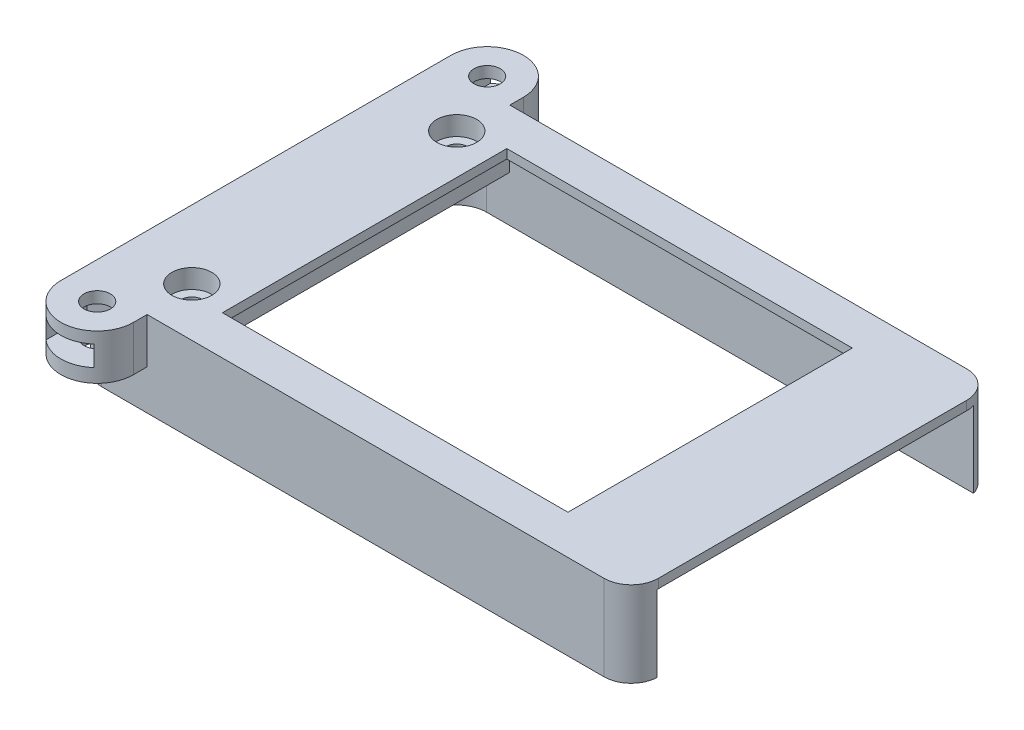
SolidWorks part; units mm, degrees
ref_plane "Front Plane" through (0, 0, 0) normal (0, 0, 1) x (1, 0, 0)
ref_plane "Top Plane" through (0, 0, 0) normal (0, 1, 0) x (1, 0, 0)
ref_plane "Right Plane" through (0, 0, 0) normal (1, 0, 0) x (0, 0, -1)
sketch "Sketch1" plane through (0, 0, 0) normal (0, 0, 1) x (1, 0, 0)
  line L0 (-23.495, -2.8321) -> (-20.447, -2.8321) construction
  line L1 (-20.447, 0) -> (-20.447, -2.8321) construction
  line L2 (-23.495, -2.8321) -> (-26.035, -2.8321) construction
  line L3 (-26.035, -2.8321) -> (-26.035, -4.4196) construction
  line L4 (-23.495, -2.8321) -> (-20.447, -2.8321) construction
  line L5 (-20.447, 0) -> (-20.447, -2.8321) construction
  line L6 (-23.495, -2.8321) -> (-26.035, -2.8321) construction
  line L7 (-26.035, -2.8321) -> (-26.035, -4.4196) construction
  line L8 (-9.4742, -6.2992) -> (-26.035, -6.2992) construction
  line L9 (-26.035, -6.2992) -> (-26.035, -4.4196) construction
  line L10 (-9.4742, -6.2992) -> (-26.035, -6.2992) construction
  line L11 (-26.035, -6.2992) -> (-26.035, -4.4196) construction
  line L12 (-20.947, 1.5) -> (-20.947, -2.8321)
  line L13 (-20.947, -2.8321) -> (-26.035, -2.8321)
  line L14 (-26.035, -2.8321) -> (-26.035, -7.9085)
  line L15 (-28.6272, -8.4085) -> (-21.9464, -8.4085) construction
  line L16 (-28.6272, -8.4085) -> (-21.9464, -8.4085) construction
  line L17 (-26.035, -7.9085) -> (-31.035, -7.9085)
  line L18 (-31.035, -7.9085) -> (-31.035, 1.5)
  line L19 (-31.035, 1.5) -> (-20.947, 1.5)
  line L20 (-20.447, 0) -> (26.0604, 0) construction
  line L21 (-20.447, 0) -> (26.0604, 0) construction
  dimension "D1" = 1
  dimension "D2" = 0.5
  dimension "D3" = 1.5
  dimension "D4" = 5
extrude "Boss-Extrude1" add sketch "Sketch1" along normal mid plane 40
sketch "Sketch2" plane through (0, 1.5, 0) normal (0, 1, 0) x (1, 0, 0)
  line L0 (-24.6493, -17.145) -> (-20.947, -17.145)
  line L1 (-20.947, -20) -> (-20.947, 20) construction
  line L2 (-20.947, -17.145) -> (-20.947, -20)
  line L3 (-20.947, -20) -> (-26.035, -20)
  line L4 (-20.947, -20) -> (-31.035, -20) construction
  line L5 (-26.035, -20) -> (-26.035, -17.145)
  line L6 (-26.035, -20) -> (-26.035, 20) construction
  line L7 (-26.035, -17.145) -> (-26.035, -15.7593)
  line L8 (-23.495, 17.895) -> (-23.495, 20)
  line L9 (-20.947, 20) -> (-31.035, 20) construction
  line L10 (-23.495, 20) -> (-26.035, 20)
  line L11 (-26.035, 20) -> (-26.035, 16.6961)
  arc A0 (-26.035, -14.605) -> (-23.495, -17.145) centre (-23.495, -14.605) ccw construction
  arc A1 (-26.035, -14.605) -> (-23.495, -17.145) centre (-23.495, -14.605) ccw construction
  arc A2 (-23.495, 17.145) -> (-26.035, 14.605) centre (-23.495, 14.605) ccw construction
  arc A3 (-23.495, 17.145) -> (-26.035, 14.605) centre (-23.495, 14.605) ccw construction
  arc A4 (-26.035, -15.7593) -> (-24.6493, -17.145) centre (-23.495, -14.605) ccw
  arc A5 (-26.285, -14.605) -> (-23.495, -17.395) centre (-23.495, -14.605) ccw construction
  arc A6 (-23.495, 17.895) -> (-26.035, 16.6961) centre (-23.495, 14.605) ccw
  arc A7 (-23.495, 17.895) -> (-26.785, 14.605) centre (-23.495, 14.605) ccw construction
  dimension "D1" = 0.25
  dimension "D2" = 0.75
extrude "Boss-Extrude2" add sketch "Sketch2" against normal up to surface (9.4085 mm away) up to face at (-28.535, -7.9085, 0)
fillet "Fillet1" radius 3 2 edges at (-31.035, -3.2043, -20) (-31.035, -3.2043, 20)
sketch "Sketch5" plane through (0, 1.5, 0) normal (0, 1, 0) x (1, 0, 0)
  line L0 (-20.947, 20) -> (27.345, 20)
  line L1 (-20.947, -20) -> (27.345, -20)
  line L2 (30.345, -17) -> (30.345, 17)
  line L3 (-20.947, -20) -> (-20.947, 20) construction
  line L4 (-20.947, -20) -> (-20.947, 20)
  line L5 (29.845, -14.605) -> (29.845, 14.605) construction
  line L8 (19.05, 15.6781) -> (19.05, -15.6781) construction
  line L9 (19.05, -15.6781) -> (-19.05, -15.6781) construction
  line L10 (19.05, 15.6781) -> (-19.05, 15.6781) construction
  line L11 (-19.05, 15.6781) -> (-19.05, -15.6781) construction
  line L12 (19.05, 15.6781) -> (19.05, -15.6781)
  line L13 (19.05, -15.6781) -> (-19.05, -15.6781)
  line L14 (19.05, 15.6781) -> (-19.05, 15.6781)
  line L15 (-19.05, 15.6781) -> (-19.05, -15.6781)
  arc A0 (27.345, -20) -> (30.345, -17) centre (27.345, -17) ccw
  arc A1 (30.345, 17) -> (27.345, 20) centre (27.345, 17) ccw
  arc A2 (-31.035, -17) -> (-28.035, -20) centre (-28.035, -17) ccw construction
  dimension "D1" = 0.5
extrude "Boss-Extrude5" add sketch "Sketch5" against normal offset from surface (1 mm away) 0.5
sketch "Sketch6" plane through (0, 0.5, 0) normal (0, -1, 0) x (1, 0, 0)
  line L0 (-23.495, 17.145) -> (27.305, 17.145) construction
  line L1 (-20.947, 17.145) -> (26.8104, 17.145)
  line L2 (26.0604, -17.145) -> (-20.447, -17.145) construction
  line L3 (-20.947, 20) -> (-20.947, -20) construction
  line L4 (-20.947, 20) -> (-20.947, 17.145)
  line L5 (27.345, 20) -> (-20.947, 20) construction
  line L6 (27.345, 20) -> (-20.947, 20)
  line L7 (-20.947, -20) -> (27.345, -20) construction
  line L8 (30.345, -17) -> (30.345, 17) construction
  line L9 (-20.947, -20) -> (27.345, -20)
  line L10 (30.345, -17) -> (30.345, 17)
  line L11 (26.0604, 17.145) -> (26.0604, 14.4018) construction
  line L12 (26.0604, 17.145) -> (26.0604, 14.4018) construction
  line L13 (26.8104, 17.145) -> (26.8104, -17.895)
  line L14 (26.0604, -17.145) -> (-20.447, -17.145) construction
  line L15 (-20.947, -20) -> (-20.947, -17.895)
  line L16 (-20.947, -17.895) -> (26.8104, -17.895)
  arc A4 (30.345, 17) -> (27.345, 20) centre (27.345, 17) ccw construction
  arc A5 (30.345, 17) -> (27.345, 20) centre (27.345, 17) ccw
  arc A6 (27.345, -20) -> (30.345, -17) centre (27.345, -17) ccw construction
  arc A7 (27.345, -20) -> (30.345, -17) centre (27.345, -17) ccw
  dimension "D2" = 1.5
extrude "Boss-Extrude6" add sketch "Sketch6" along normal up to surface (3.3321 mm away)
sketch "Sketch7" plane through (0, -2.8321, 0) normal (0, -1, 0) x (1, 0, 0)
  line L1 (-20.947, 20) -> (27.345, 20)
  line L2 (-20.947, 20) -> (-20.947, 17.145)
  line L3 (-20.947, 17.145) -> (30.3415, 17.145)
  line L6 (-23.495, -20) -> (27.345, -20)
  line L7 (-23.495, -20) -> (-23.495, -17.895)
  line L8 (-23.495, -17.895) -> (30.2084, -17.895)
  arc A0 (30.345, 17) -> (27.345, 20) centre (27.345, 17) ccw construction
  arc A1 (27.345, -20) -> (30.345, -17) centre (27.345, -17) ccw construction
  arc A2 (30.3415, 17.145) -> (27.345, 20) centre (27.345, 17) ccw
  arc A3 (27.345, -20) -> (30.2084, -17.895) centre (27.345, -17) ccw
extrude "Boss-Extrude7" add sketch "Sketch7" along normal up to surface (5.0764 mm away) up to face at (-25.9315, -7.9085, 1.3908)
sketch "Sketch9" plane through (0, 1.5, 0) normal (0, 1, 0) x (1, 0, 0)
  line L0 (-31.035, 17) -> (-31.035, 21.5)
  line L1 (-23.035, 21.5) -> (-23.035, 20)
  line L2 (27.345, 20) -> (-28.035, 20) construction
  line L3 (-23.035, 20) -> (-28.035, 20)
  line L4 (0, 0) -> (-7.0217, 0) construction
  line L5 (-23.035, -20) -> (-28.035, -20)
  line L6 (-23.035, -21.5) -> (-23.035, -20)
  line L7 (-31.035, -17) -> (-31.035, -21.5)
  arc A0 (-31.035, 21.5) -> (-23.035, 21.5) centre (-27.035, 21.5) cw
  arc A1 (-28.035, 20) -> (-31.035, 17) centre (-28.035, 17) ccw
  arc A2 (-28.035, -20) -> (-31.035, -17) centre (-28.035, -17) cw
  arc A3 (-31.035, -21.5) -> (-23.035, -21.5) centre (-27.035, -21.5) ccw
  dimension "D1" = 8
  dimension "D2" = 1.5
extrude "Boss-Extrude8" add sketch "Sketch9" against normal blind 5
hole_wizard "M2.5 Clearance Hole1" positions "Sketch10" profile "Sketch11" hole size "M2.5" standard "ANSI Metric" end condition through all
sketch "Sketch10" plane through (0, 1.5, 0) normal (0, 1, 0) x (1, 0, 0)
  point P0 (-27.035, -21.5)
  point P3 (-27.035, 21.5)
sketch "Sketch11" plane through (-27.035, 1.5, 21.5) normal (1, 0, 0) x (0, 0, 1)
  line L0 (0, 0) -> (0, 9.4085)
  line L1 (0, 9.4085) -> (1.45, 9.4085)
  line L2 (1.45, 9.4085) -> (1.45, 0)
  line L5 (1.45, 0) -> (0, 0)
  line L11 (0, -6.35) -> (0, 107.95) construction
  dimension "Thru Hole Dia." = 2.9
  dimension "Thru Hole Depth" = 9.4085
ref_plane "Plane1" through (0, -2, 0) normal (0, 1, 0) x (1, 0, 0)
sketch "Sketch12" plane through (0, -2, 0) normal (0, 1, 0) x (1, 0, 0)
  line L0 (-29.685, -23.03) -> (-29.685, -29.56)
  line L1 (-24.385, -23.03) -> (-24.385, -19.97)
  line L2 (-24.385, -19.97) -> (-27.035, -18.44)
  line L3 (-27.035, -18.44) -> (-29.685, -19.97)
  line L4 (-29.685, -19.97) -> (-29.685, -23.03)
  line L5 (-29.685, -23.03) -> (-27.035, -24.56) construction
  line L6 (-27.035, -24.56) -> (-24.385, -23.03) construction
  line L13 (-29.685, -29.56) -> (-24.385, -29.56)
  line L14 (-24.385, -29.56) -> (-24.385, -23.03)
  line L15 (0, 0) -> (-12.2155, 0) construction
  line L16 (-29.685, 23.03) -> (-29.685, 29.56)
  line L17 (-29.685, 29.56) -> (-24.385, 29.56)
  line L18 (-24.385, 29.56) -> (-24.385, 23.03)
  line L19 (-24.385, 23.03) -> (-24.385, 19.97)
  line L20 (-24.385, 19.97) -> (-27.035, 18.44)
  line L21 (-27.035, 18.44) -> (-29.685, 19.97)
  line L22 (-29.685, 19.97) -> (-29.685, 23.03)
  circle A0 centre (-27.035, -21.5) radius 2.65 construction
  circle A2 centre (-27.035, -21.5) radius 2.5 construction
  dimension "D1" = 5
  dimension "D2" = 0.15
  dimension "D3" = 5
extrude "Cut-Extrude1" cut sketch "Sketch12" along normal blind 2.25
sketch "Sketch13" plane through (0, 1.5, 0) normal (0, 1, 0) x (1, 0, 0)
  circle A0 centre (-23.495, 14.605) radius 1.016 construction
  circle A1 centre (-23.495, -14.605) radius 1.016 construction
  circle A2 centre (27.305, -14.605) radius 1.016 construction
  circle A3 centre (27.305, 14.605) radius 1.016 construction
  circle A4 centre (-23.495, 14.605) radius 1.016
  circle A5 centre (-23.495, -14.605) radius 1.016
  circle A6 centre (27.305, -14.605) radius 1.016
  circle A7 centre (27.305, 14.605) radius 1.016
hole_wizard "CBORE for M2 SHCS1" positions "Sketch14" profile "Sketch15" counterbore size "M2" standard "ANSI Metric" end condition through all
sketch "Sketch14" plane through (0, 1.5, 0) normal (0, 1, 0) x (1, 0, 0)
  point P0 (-23.495, -14.605)
  point P3 (-23.495, 14.605)
sketch "Sketch15" plane through (-23.495, 1.5, 14.605) normal (1, 0, 0) x (0, 0, 1)
  line L0 (0, 0) -> (0, 9.4085)
  line L1 (0, 9.4085) -> (1.2, 9.4085)
  line L3 (1.2, 9.4085) -> (1.2, 2.1)
  line L4 (1.2, 2.1) -> (2.2, 2.1)
  line L5 (2.2, 2.1) -> (2.2, 0)
  line L7 (2.2, 0) -> (0, 0)
  line L11 (0, -6.35) -> (0, 107.95) construction
  dimension "Thru Hole Dia." = 2.4
  dimension "Thru Hole Depth" = 9.4085
  dimension "C'Bore Dia." = 4.4
  dimension "C'Bore Depth" = 2.1
sketch "Sketch16" plane through (26.8104, 0, 0) normal (-1, 0, 0) x (0, 0, 1)
  line L4 (-17.895, 0.5) -> (-17.895, -2.8321)
  line L5 (-17.895, -2.8321) -> (17.145, -2.8321)
  line L6 (17.145, -2.8321) -> (17.145, 0.5)
  line L7 (17.145, 0.5) -> (-17.895, 0.5)
  line L8 (-17.895, 0.5) -> (-17.895, -2.8321)
  line L9 (-17.895, -2.8321) -> (17.145, -2.8321)
  line L10 (17.145, -2.8321) -> (17.145, 0.5)
  line L11 (17.145, 0.5) -> (-17.895, 0.5)
  dimension "D1" = 0
extrude "Cut-Extrude2" cut sketch "Sketch16" against normal through all
